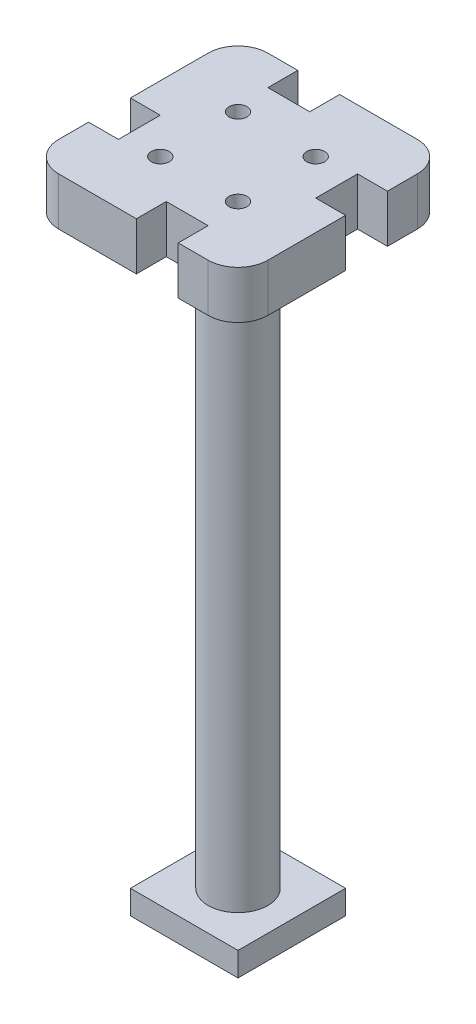
SolidWorks part; units mm, degrees
ref_plane "Front Plane" through (0, 0, 0) normal (0, 0, 1) x (1, 0, 0)
ref_plane "Top Plane" through (0, 0, 0) normal (0, 1, 0) x (1, 0, 0)
ref_plane "Right Plane" through (0, 0, 0) normal (1, 0, 0) x (0, 0, -1)
sketch "Sketch1" plane through (0, 0, 0) normal (0, 1, 0) x (1, 0, 0)
  line L1 (0, 0) -> (35, 0)
  line L2 (0, 0) -> (0, 35)
  line L3 (0, 35) -> (35, 35)
  line L4 (35, 0) -> (35, 35)
  dimension "D1" = 35
  dimension "D2" = 35
extrude "Boss-Extrude1" add sketch "Sketch1" along normal blind 8
sketch "Sketch2" plane through (0, 0, 0) normal (0, -1, 0) x (1, 0, 0)
  line L0 (0, 0) -> (35, 0) construction
  line L1 (18, 0) -> (25, 0)
  line L2 (18, 0) -> (18, -5)
  line L3 (18, -5) -> (25, -5)
  line L4 (25, 0) -> (25, -5)
  line L5 (35, -35) -> (0, -35) construction
  line L6 (10, -35) -> (17, -35)
  line L7 (10, -35) -> (10, -30)
  line L8 (10, -30) -> (17, -30)
  line L9 (17, -35) -> (17, -30)
  line L10 (0, -35) -> (0, 0) construction
  line L11 (0, -10) -> (5, -10)
  line L12 (0, -10) -> (0, -17)
  line L13 (0, -17) -> (5, -17)
  line L14 (5, -10) -> (5, -17)
  line L15 (35, 0) -> (35, -35) construction
  line L16 (35, -18) -> (30, -18)
  line L17 (35, -18) -> (35, -25)
  line L18 (35, -25) -> (30, -25)
  line L19 (30, -18) -> (30, -25)
  circle A0 centre (6, -6) radius 2.5
  circle A1 centre (29, -6) radius 4
  circle A2 centre (6, -29) radius 4
  circle A3 centre (29, -29) radius 2.5
  circle A4 centre (17.5, -17.5) radius 5
  circle A5 centre (11, -11) radius 1.5
  circle A6 centre (24, -11) radius 1.5
  circle A7 centre (24, -24) radius 1.5
  circle A8 centre (11, -24) radius 1.5
  point P45 (17.5, 0)
  point P46 (35, -17.5)
  line M26 (0, 0) -> (0, -35)
  line M27 (0, -35) -> (35, -35)
  line M28 (35, -35) -> (35, 0)
  line M29 (35, 0) -> (0, 0)
  dimension "D7" = 5
  dimension "D8" = 5
  dimension "D9" = 8
  dimension "D10" = 8
  dimension "D11" = 10
  dimension "D12" = 3
  dimension "D13" = 3
  dimension "D14" = 3
  dimension "D15" = 3
  dimension "D1" = 5
  dimension "D2" = 7
  dimension "D3" = 10
  dimension "D4" = 10
  dimension "D5" = 10
  dimension "D6" = 10
  dimension "D16" = 6
  dimension "D17" = 6
  dimension "D18" = 6
  dimension "D19" = 6
  dimension "D20" = 6
  dimension "D21" = 6
  dimension "D22" = 6
  dimension "D23" = 11
  dimension "D24" = 6
  dimension "D25" = 11
extrude "Cut-Extrude1" cut sketch "Sketch2" against normal through all contours L16 L19 L18 M28 | L9 L8 L7 M27 | L14 L11 L13 M26 | L4 L2 L3 M29 | A5 | A6 | A8 | A7 region at (21.5, 0, -2.5) region at (2.5, 0, -13.5) region at (32.5, 0, -21.5) region at (13.5, 0, -32.5) region at (11, 0, -11) region at (24, 0, -11) region at (24, 0, -24) region at (11, 0, -24)
extrude "Cut-Extrude2" cut sketch "Sketch2<5>" against normal blind 4 contours A2 | A1 | A5 region at (6, 0, -29)
sketch "Sketch2<5>" plane through (0, 0, 0) normal (0, -1, 0) x (1, 0, 0) same geometry as "Sketch2"
extrude "Boss-Extrude2" add sketch "Sketch2<7>" along normal blind 98 contours A4 region at (17.5, 0, -17.5)
sketch "Sketch2<7>" plane through (0, 0, 0) normal (0, -1, 0) x (1, 0, 0) same geometry as "Sketch2"
sketch "Sketch4" plane through (0, -98, 0) normal (0, -1, 0) x (1, 0, 0)
  line L0 (0, -10) -> (0, 0) construction
  line L1 (8.5, -8.5) -> (26.5, -8.5)
  line L2 (8.5, -8.5) -> (8.5, -26.5)
  line L3 (8.5, -26.5) -> (26.5, -26.5)
  line L4 (26.5, -8.5) -> (26.5, -26.5)
  line L5 (35, -35) -> (17, -35) construction
  dimension "D1" = 18
  dimension "D2" = 18
  dimension "D3" = 8.5
  dimension "D4" = 8.5
extrude "Boss-Extrude3" add sketch "Sketch4" along normal blind 4
fillet "Fillet2" radius 5 4 edges at (35, 4, 0) (35, 4, -35) (0, 4, -35) (0, 4, 0)
